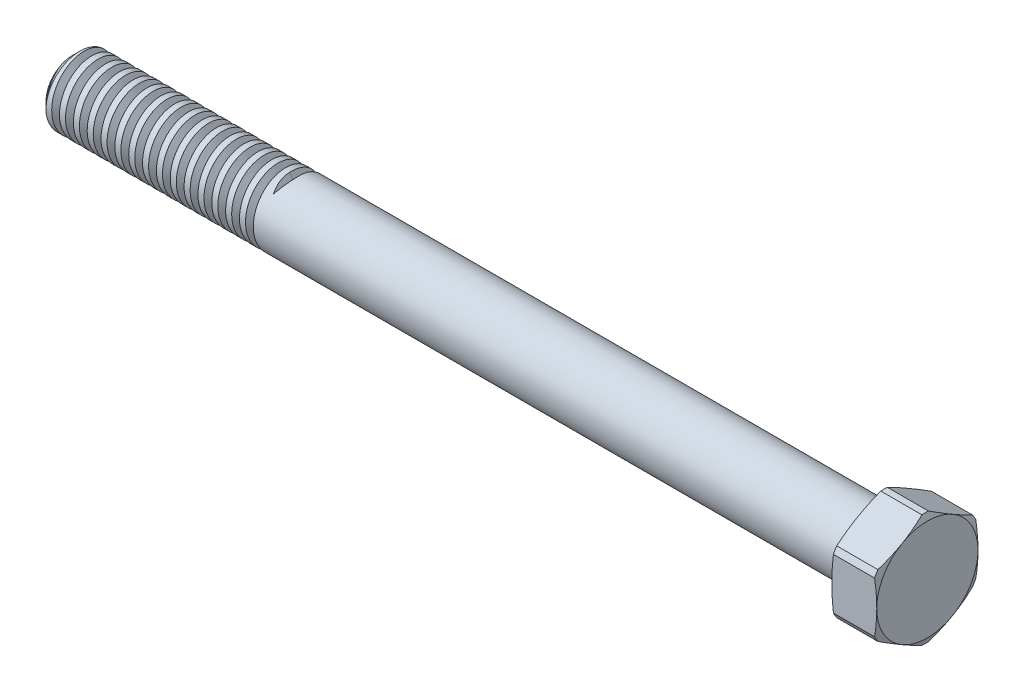
SolidWorks part; units mm, degrees
material "Cast Alloy Steel"
ref_plane "Front Plane" through (0, 0, 0) normal (0, 0, 1) x (1, 0, 0)
ref_plane "Top Plane" through (0, 0, 0) normal (0, 1, 0) x (1, 0, 0)
ref_plane "Right Plane" through (0, 0, 0) normal (1, 0, 0) x (0, 0, -1)
sketch "Sketch1" plane through (0, 0, 0) normal (0, 0, 1) x (1, 0, 0)
  line L0 (60.325, 0) -> (-60.325, 0) construction
  line L1 (-60.325, 0) -> (-60.325, 3.7465)
  line L2 (-59.309, 4.7625) -> (53.975, 4.7625)
  line L3 (53.975, 4.7625) -> (53.975, 7.12)
  line L4 (53.975, 7.12) -> (54.2094, 7.9949)
  line L5 (54.2094, 7.9949) -> (60.0152, 7.9949)
  line L6 (60.0152, 7.9949) -> (60.325, 7.1437)
  line L7 (60.325, 7.1437) -> (60.325, 0)
  line L8 (56.7531, 6.1867) -> (60.325, 8.2489) construction
  line L9 (60.325, 8.2489) -> (63.8969, 6.1867) construction
  line L10 (-60.325, 3.7465) -> (-59.309, 4.7625)
  line L11 (-60.325, 0) -> (60.325, 0)
  circle A0 centre (60.325, 0) radius 7.1437 construction
  point P4 (0, 0)
  point P5 (-60.325, 4.7625)
  dimension "D1" = 9.525
  dimension "D2" = 114.3
  dimension "D3" = 6.35
  dimension "D4" = 14.2875
  dimension "D5" = 60
  dimension "D6" = 15
  dimension "D7" = 20
  dimension "D8" = 0.254
revolve "Revolve1" add sketch "Sketch1" angle 360 about L11
sketch "Sketch2" plane through (60.325, 0, 0) normal (1, 0, 0) x (0, 0, -1)
  line L1 (0, 8.2489) -> (-7.1437, 4.1244)
  line L2 (-7.1437, 4.1244) -> (-7.1437, -4.1244)
  line L3 (-7.1437, -4.1244) -> (0, -8.2489)
  line L4 (0, -8.2489) -> (7.1437, -4.1244)
  line L5 (7.1437, -4.1244) -> (7.1437, 4.1244)
  line L6 (7.1437, 4.1244) -> (0, 8.2489)
  circle A0 centre (0, 0) radius 7.1437 construction
  circle A2 centre (0, 0) radius 7.1437 construction
extrude "Cut-Extrude1" cut sketch "Sketch2" against normal through all flip side to cut
sketch "Sketch3" plane through (-60.325, 0, 0) normal (-1, 0, 0) x (0, 0, 1)
  circle A0 centre (0, 0) radius 4.7625 construction
  circle A1 centre (0, 0) radius 4.7625
curve "Helix/Spiral1" pitch 1.9538 height 31.75 radius 4.7625 centre (-60.325, 0, 0) axis (1, 0, 0) start towards (0, -1, 0)
sketch "Sketch4" plane through (0, 0, 0) normal (0, 1, 0) x (1, 0, 0)
  line L0 (-60.325, 4.7625) -> (-61.4249, 4.7625)
  line L1 (-61.4249, 4.7625) -> (-60.8749, 3.81)
  line L2 (-60.8749, 3.81) -> (-60.325, 4.7625)
  line L3 (53.975, 4.7625) -> (-59.309, 4.7625) construction
  line L6 (-60.325, 0) -> (60.325, 0) construction
  line L7 (-60.325, 3.7465) -> (-60.325, -3.7465) construction
  line L8 (60.325, -3.5719) -> (60.325, 3.5719) construction
  dimension "D1" = 60
  dimension "D2" = 7.62
sweep "Cut-Sweep1" cut profiles "Sketch4" path "Helix/Spiral1" align with end faces yes
sketch "Sketch5" plane through (0, 0, 0) normal (0, 0, -1) x (-1, 0, 0)
  line L3 (29.6749, 4.7625) -> (28.575, 4.7625)
  line L4 (28.575, 4.7625) -> (29.1249, 3.81)
  line L5 (29.1249, 3.81) -> (29.6749, 4.7625)
  line L6 (29.6749, 4.7625) -> (28.575, 4.7625)
  line L7 (28.575, 4.7625) -> (29.1249, 3.81)
  line L8 (29.1249, 3.81) -> (29.6749, 4.7625)
  dimension "D1" = 0
extrude "Cut-Extrude2" cut sketch "Sketch5" against normal through all
fillet "Fillet1" [suppressed] radius 1.27
